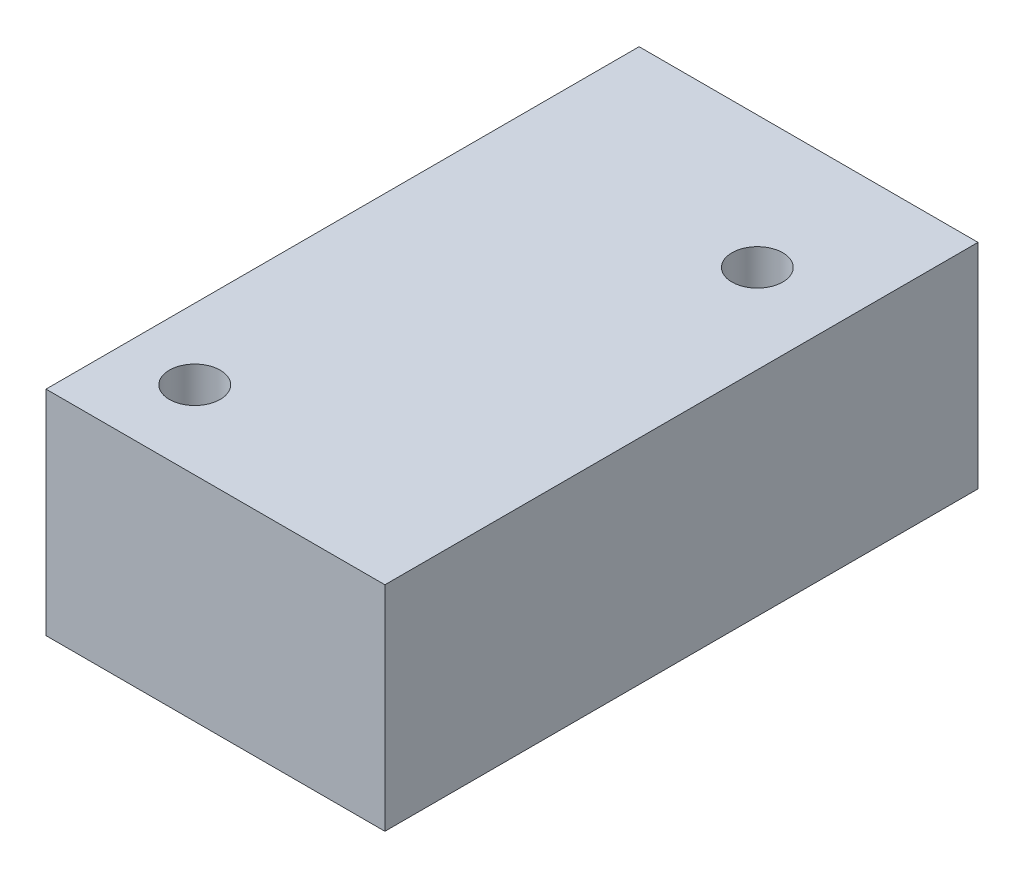
SolidWorks part; units mm, degrees
ref_plane "Front Plane" through (0, 0, 0) normal (0, 0, 1) x (1, 0, 0)
ref_plane "Top Plane" through (0, 0, 0) normal (0, 1, 0) x (1, 0, 0)
ref_plane "Right Plane" through (0, 0, 0) normal (1, 0, 0) x (0, 0, -1)
sketch "Sketch1" plane through (0, 0, 0) normal (0, 1, 0) x (1, 0, 0)
  line L1 (-10, 17.5) -> (10, 17.5)
  line L2 (-10, 17.5) -> (-10, -17.5)
  line L3 (-10, -17.5) -> (10, -17.5)
  line L4 (10, 17.5) -> (10, -17.5)
  line L5 (-10, 17.5) -> (10, -17.5) construction
  line L6 (-10, -17.5) -> (10, 17.5) construction
  point P0 (0, 0)
  dimension "D1" = 20
  dimension "D2" = 35
extrude "Boss-Extrude1" add sketch "Sketch1" along normal blind 12.6
sketch "Sketch2" plane through (0, 0, 0) normal (0, -1, 0) x (1, 0, 0)
  circle A0 centre (-5.8311, 12.8901) radius 1.5 construction
  circle A1 centre (4.7689, -9.7099) radius 1.5 construction
  circle A2 centre (-5.8311, 12.8901) radius 1.5
  circle A3 centre (4.7689, -9.7099) radius 1.5
extrude "Cut-Extrude1" cut sketch "Sketch2" against normal up to next
